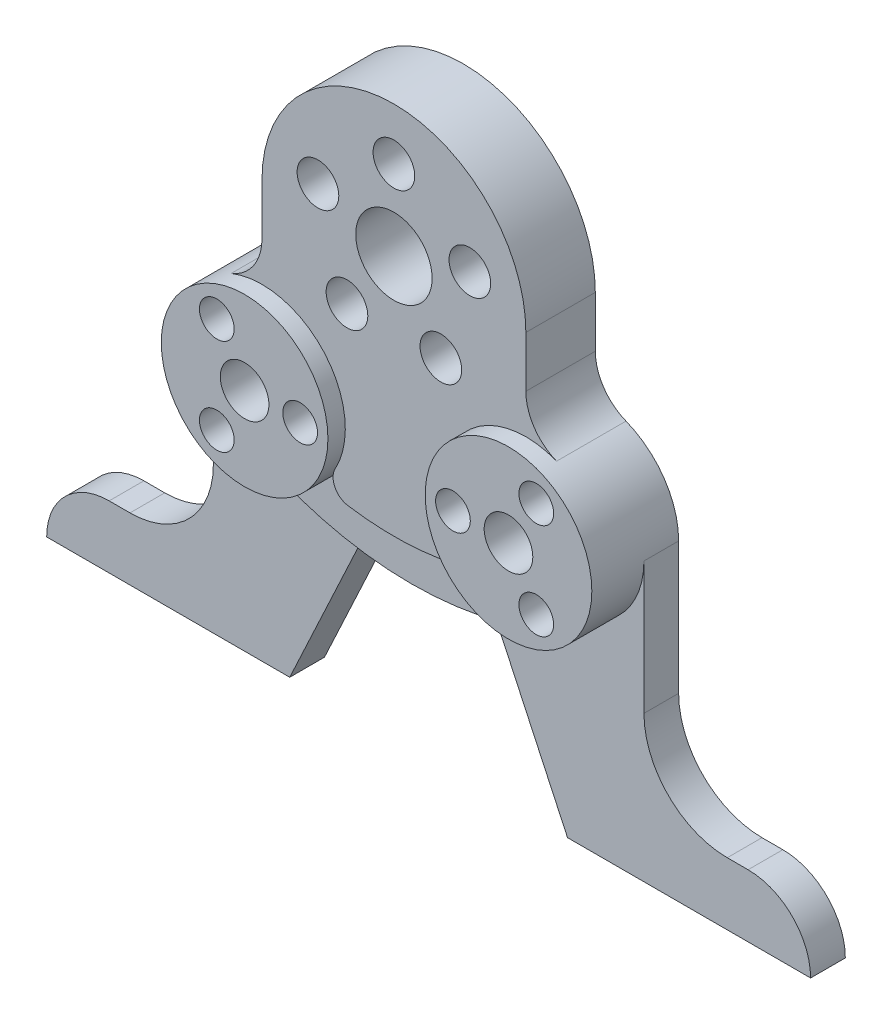
SolidWorks part; units mm, degrees
ref_plane "Спереди" through (0, 0, 0) normal (0, 0, 1) x (1, 0, 0)
ref_plane "Сверху" through (0, 0, 0) normal (0, 1, 0) x (1, 0, 0)
ref_plane "Справа" through (0, 0, 0) normal (1, 0, 0) x (0, 0, -1)
sketch "Эскиз1" plane through (0, 0, 0) normal (0, 0, 1) x (1, 0, 0)
  line L0 (0, 61.3547) -> (0, -91.3769) construction
  line L1 (-54.7424, 0) -> (74.7352, 0) construction
  line L2 (-38, 0) -> (-38, -14.673)
  line L3 (38, 0) -> (38, -14.673)
  line L4 (3.8199, -50) -> (62, -50) construction
  line L5 (38, -27.6882) -> (38, -76.6807) construction
  line L6 (-3.8199, -50) -> (-62, -50) construction
  line L7 (-38, -27.6882) -> (-38, -76.6807) construction
  line L8 (62, -50) -> (62, -88)
  line L9 (86, -112) -> (92, -112)
  line L10 (40, -130) -> (110, -130)
  line L11 (40, -130) -> (20.4132, -87.996)
  line L12 (-40, -130) -> (-110, -130)
  line L13 (-40, -130) -> (-20.4132, -87.996)
  line L14 (-62, -50) -> (-62, -88)
  line L15 (-86, -112) -> (-92, -112)
  line L16 (-38, -26) -> (-38, -27.6882)
  arc A0 (38, 0) -> (-38, 0) centre (0, 0) ccw
  circle A1 centre (0, 23) radius 6
  circle A2 centre (21.8743, 7.1074) radius 6
  circle A3 centre (13.5191, -18.6074) radius 6
  circle A4 centre (-13.5191, -18.6074) radius 6
  circle A5 centre (-21.8743, 7.1074) radius 6
  circle A6 centre (0, 0) radius 11
  circle A7 centre (38, -50) radius 24
  arc A8 (38, -14.673) -> (46.8421, -27.6882) centre (52, -14.673) ccw
  circle A9 centre (22, -50) radius 5
  circle A10 centre (46, -36.1436) radius 5
  circle A11 centre (46, -63.8564) radius 5
  circle A12 centre (38, -50) radius 7
  circle A13 centre (-46, -63.8564) radius 5
  circle A14 centre (-38, -50) radius 7
  circle A15 centre (-22, -50) radius 5
  circle A16 centre (-46, -36.1436) radius 5
  circle A17 centre (-38, -50) radius 24
  arc A18 (-38, -14.673) -> (-46.8421, -27.6882) centre (-52, -14.673) cw
  arc A19 (13.3073, -68.7948) -> (16.9168, -61.4674) centre (12.5245, -63.8564) ccw
  arc A20 (-13.3073, -68.7948) -> (-16.9168, -61.4674) centre (-12.5245, -63.8564) cw
  arc A22 (-50, -70.7846) -> (50, -70.7846) centre (0, 15.8179) ccw
  arc A23 (62, -88) -> (86, -112) centre (86, -88) ccw
  arc A24 (110, -130) -> (92, -112) centre (92, -130) ccw
  arc A25 (20.4132, -87.996) -> (12.1877, -83.4366) centre (13.1628, -91.3769) ccw
  arc A26 (-20.4132, -87.996) -> (-12.1877, -83.4366) centre (-13.1628, -91.3769) cw
  arc A27 (-62, -88) -> (-86, -112) centre (-86, -88) cw
  arc A28 (-110, -130) -> (-92, -112) centre (-92, -130) cw
  arc A29 (-13.3073, -68.7948) -> (13.3073, -68.7948) centre (0, 15.1571) ccw
  point P19 (0, 0)
  point P38 (38, -50)
  dimension "D1" = 76
  dimension "D2" = 12
  dimension "D5" = 22
  dimension "D7" = 48
  dimension "D8" = 14
  dimension "D10" = 10
  dimension "D12" = 14
  dimension "D13" = 5
  dimension "D14" = 85
  dimension "D15" = 200
  dimension "D16" = 18
  dimension "D18" = 24
  dimension "D19" = 36
  dimension "D22" = 16
  dimension "D3" = 23
  dimension "D6" = 50
  dimension "D9" = 16
  dimension "D17" = 130
  dimension "D20" = 92
  dimension "D21" = 40
  dimension "D23" = 65
  dimension "D4" = 5
  dimension "D11" = 3
extrude "Бобышка-Вытянуть1" add sketch "Эскиз1" along normal blind 10 contours A25 L11 L10 A24 L9 A23 L8 A7 A22 | A28 L12 L13 A26 A22 A17 L14 A27 L15 region at (-57.3562, -105.0327, 0) region at (57.3562, -105.0327, 0)
extrude "Бобышка-Вытянуть2" add sketch "Эскиз1<3>" along normal blind 20 separate body contours A20 A29 A19 A7 A8 L3 A0 L2 A18 A17 A1 A2 A3 A4 A5 A6 region at (0, -12.2949, 0)
sketch "Эскиз1<3>" plane through (0, 0, 0) normal (0, 0, 1) x (1, 0, 0) same geometry as "Эскиз1"
extrude "Бобышка-Вытянуть3" add sketch "Эскиз1<4>" along normal blind 15 contours A29 A20 A17 A22 A7 A19 region at (0, -75.6982, 0)
sketch "Эскиз1<4>" plane through (0, 0, 0) normal (0, 0, 1) x (1, 0, 0) same geometry as "Эскиз1"
extrude "Бобышка-Вытянуть4" add sketch "Эскиз1<5>" along normal blind 25 contours A17 A15 A13 A14 A16 | A7 A12 A11 A10 A9 region at (-42.3736, -27.0926, 0) region at (57.2906, -36.8946, 0)
sketch "Эскиз1<5>" plane through (0, 0, 0) normal (0, 0, 1) x (1, 0, 0) same geometry as "Эскиз1"
